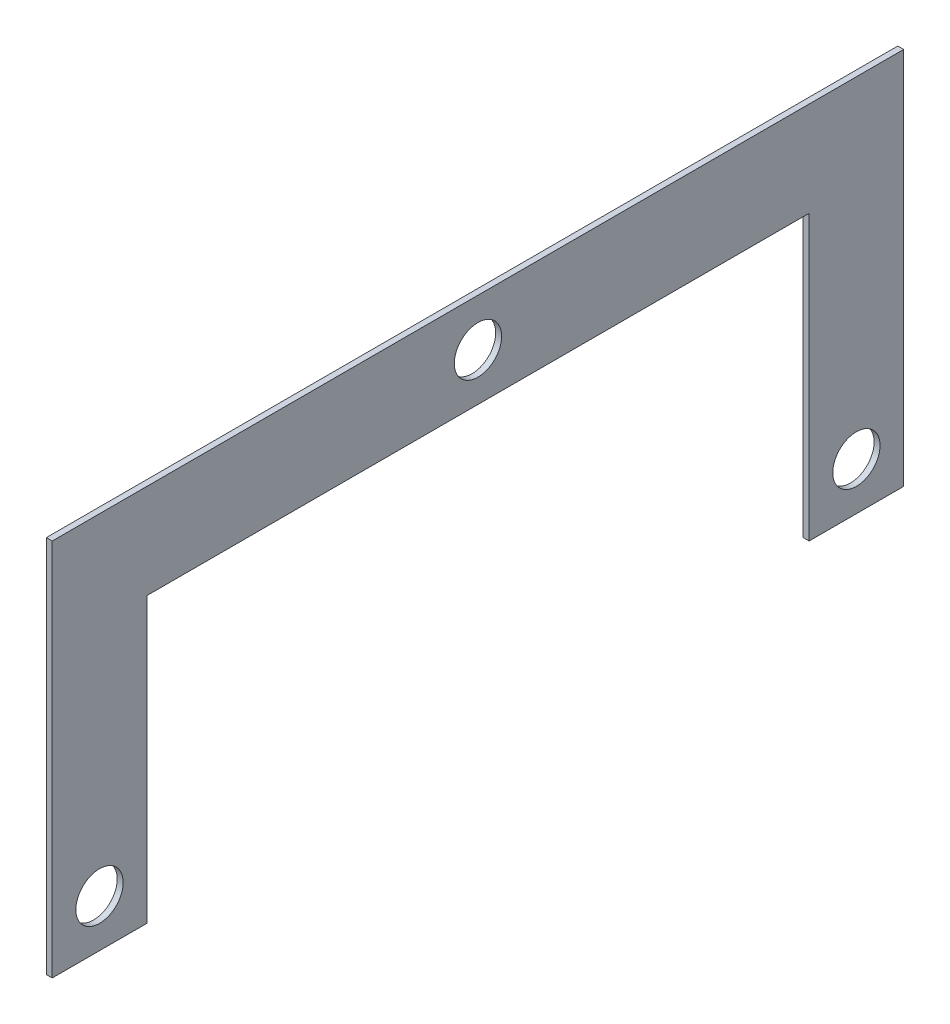
SolidWorks part; units mm, degrees
material "6063-O"
ref_plane "Front" through (0, 0, 0) normal (0, 0, 1) x (1, 0, 0)
ref_plane "Top" through (0, 0, 0) normal (0, 1, 0) x (1, 0, 0)
ref_plane "Right" through (0, 0, 0) normal (1, 0, 0) x (0, 0, -1)
sketch "Sketch1" plane through (0, 0, 0) normal (1, 0, 0) x (0, 0, -1)
  line L0 (0, 25.4) -> (0, -25.4) construction
  line L1 (-228.6, 25.4) -> (228.6, 25.4)
  line L2 (-228.6, 25.4) -> (-228.6, -177.8)
  line L3 (-177.8, -25.4) -> (177.8, -25.4)
  line L4 (228.6, 25.4) -> (228.6, -177.8)
  line L7 (228.6, -177.8) -> (177.8, -177.8)
  line L8 (177.8, -25.4) -> (177.8, -177.8)
  line L11 (-228.6, -177.8) -> (-177.8, -177.8)
  line L12 (-177.8, -25.4) -> (-177.8, -177.8)
  circle A0 centre (0, 0) radius 12.7
  point P12 (0, 0)
  dimension "D5" = 25.4
  dimension "D1" = 50.8
  dimension "D2" = 50.8
  dimension "D3" = 457.2
  dimension "D4" = 152.4
extrude "Boss-Extrude1" add sketch "Sketch1" along normal blind 3.175
sketch "Sketch2" plane through (3.175, 0, 0) normal (1, 0, 0) x (0, 0, -1)
  line L0 (-355.1905, -127) -> (49644.8095, -127) construction
  line L1 (-228.6, -177.8) -> (-177.8, -177.8) construction
  dimension "D1" = 50.8
sketch "Sketch3" plane through (3.175, 0, 0) normal (1, 0, 0) x (0, 0, -1)
  line L0 (-279.2989, -152.4) -> (49720.7011, -152.4) construction
  line L1 (-228.6, -177.8) -> (-177.8, -177.8) construction
  line L2 (-203.2, -177.8) -> (-203.2, 25.4) construction
  line L3 (228.6, 25.4) -> (-228.6, 25.4) construction
  line L4 (203.2, -177.8) -> (203.2, 25.4) construction
  line L5 (177.8, -177.8) -> (228.6, -177.8) construction
  circle A0 centre (-203.2, -152.4) radius 12.7
  circle A1 centre (203.2, -152.4) radius 12.7
  point P12 (-203.2, -152.4)
  point P13 (203.2, -152.4)
  dimension "D2" = 25.4
  dimension "D1" = 25.4
extrude "Cut-Extrude1" cut sketch "Sketch3" against normal through all
